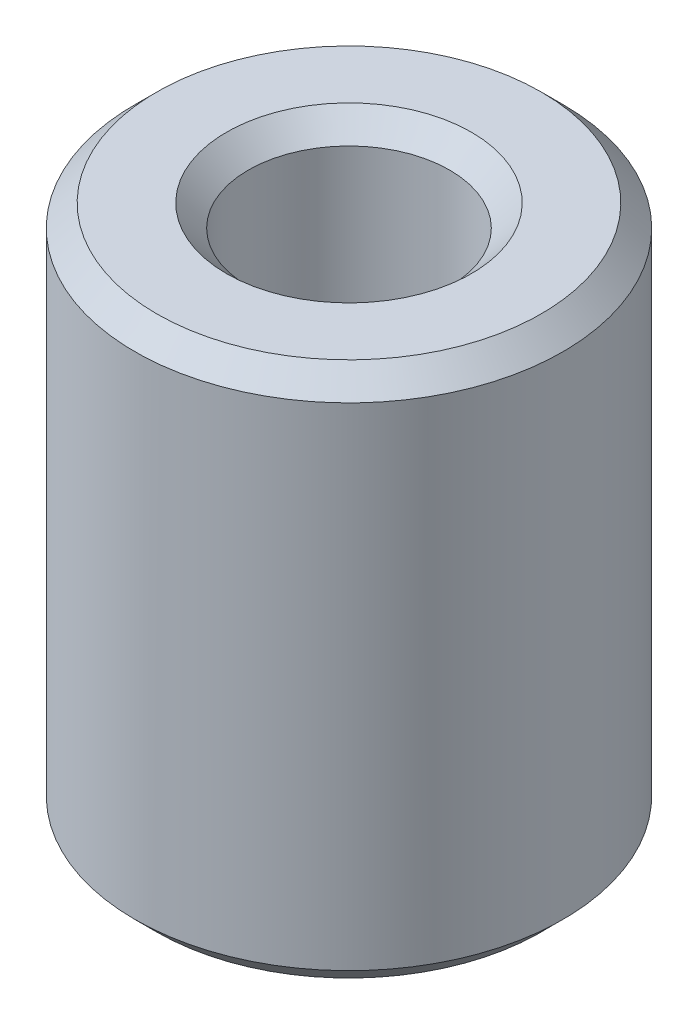
SolidWorks part; units mm, degrees
ref_plane "Front Plane" through (0, 0, 0) normal (0, 0, 1) x (1, 0, 0)
ref_plane "Top Plane" through (0, 0, 0) normal (0, 1, 0) x (1, 0, 0)
ref_plane "Right Plane" through (0, 0, 0) normal (1, 0, 0) x (0, 0, -1)
sketch "Sketch1" plane through (0, 0, 0) normal (0, 1, 0) x (1, 0, 0)
  circle A0 centre (0, 0) radius 5
  dimension "SLEEVE_OD" = 10
extrude "Boss-Extrude1" add sketch "Sketch1" along normal blind 12.5054
sketch "Sketch2" plane through (0, 0, 0) normal (0, 1, 0) x (1, 0, 0)
  circle A0 centre (0, 0) radius 2.3514
  dimension "BORE_D" = 4.7028
extrude "Cut-Extrude1" cut sketch "Sketch2" along normal through all
chamfer "Chamfer1" distance 0.5102 angle 45 4 edges at (0, 12.5054, 2.3514) (0, 0, 2.3514) (0, 0, 5) (0, 12.5054, 5)
